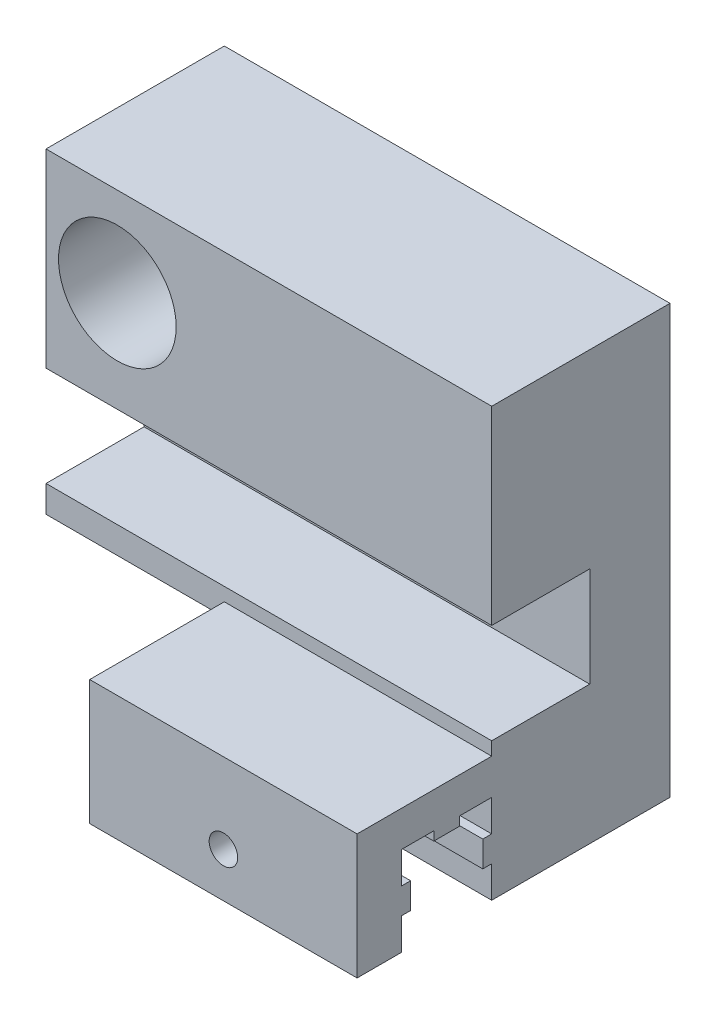
SolidWorks part; units mm, degrees
ref_plane "Front Plane" through (0, 0, 0) normal (0, 0, 1) x (1, 0, 0)
ref_plane "Top Plane" through (0, 0, 0) normal (0, 1, 0) x (1, 0, 0)
ref_plane "Right Plane" through (0, 0, 0) normal (1, 0, 0) x (0, 0, -1)
sketch "Esquisse1" plane through (0, 0, 0) normal (0, 0, 1) x (1, 0, 0)
  line L0 (25, 17.5) -> (25, -17.5)
  line L1 (-25, 17.5) -> (25, 17.5)
  line L2 (-25, 17.5) -> (-25, -17.5)
  line L3 (-25, -17.5) -> (25, -17.5)
  point P4 (-25, 0)
  point P6 (0, -17.5)
  point P7 (-9.098, 0)
  point P8 (13.0211, -17.5)
  point P9 (12.1692, -17.5)
  dimension "D3" = 35
  dimension "D4" = 50
extrude "Main Extrusion" add sketch "Esquisse1" along normal blind 20
sketch "Esquisse5" plane through (0, 0, 20) normal (0, 0, 1) x (1, 0, 0)
  line L1 (-25, -17.5) -> (25, -17.5) construction
  line L3 (-25, 17.5) -> (-25, -17.5) construction
  circle A0 centre (-17, 7.5) radius 1.6
  dimension "D1" = 3.2
  dimension "D2" = 25
  dimension "D3" = 8
extrude "Gear Linear Holes" cut sketch "Esquisse5" against normal through all
sketch "Esquisse8" plane through (0, 0, 0) normal (1, 0, 0) x (0, 0, -1)
  line L0 (-20, -20.5) -> (-20, -24.05)
  line L1 (-20, -20.5) -> (-23.6, -20.5)
  line L2 (-23.6, -20.5) -> (-23.6, -21.5)
  line L3 (-23.6, -21.5) -> (-26.5, -21.5)
  line L4 (-26.5, -21.5) -> (-26.5, -20.5)
  line L5 (-35.1, -16.5) -> (0, -16.5)
  line L6 (-20, -30.5) -> (0, -30.5)
  line L7 (0, -30.5) -> (0, -16.5)
  line L8 (0, -17.5) -> (0, 17.5) construction
  line L9 (-26.5, -20.5) -> (-30.1, -20.5)
  line L10 (-20, -17.5) -> (0, -17.5) construction
  line L12 (0, 17.5) -> (0, -17.5) construction
  line L13 (-30.1, -20.5) -> (-30.1, -24.05)
  line L14 (-30.1, -30.5) -> (-35.1, -30.5)
  line L15 (-35.1, -30.5) -> (-35.1, -16.5)
  line L16 (-20, -24.05) -> (-21, -24.05)
  line L17 (-21, -24.05) -> (-21, -26.95)
  line L18 (-21, -26.95) -> (-20, -26.95)
  line L19 (-20, -26.95) -> (-20, -30.5)
  line L21 (-30.1, -24.05) -> (-29.1, -24.05)
  line L22 (-29.1, -24.05) -> (-29.1, -26.95)
  line L23 (-29.1, -26.95) -> (-30.1, -26.95)
  line L24 (-30.1, -26.95) -> (-30.1, -30.5)
  line L25 (-20, 17.5) -> (-20, -17.5) construction
  point P12 (-17.324, -31.1687)
  point P18 (0, -17.5)
  point P19 (0, -15.4707)
  point P21 (0, 0)
  point P26 (-26.4545, -30.5)
  point P28 (-33.3936, -30.5)
  point P29 (0, 0)
  point P35 (0, -14.728)
  dimension "D1" = 2.9
  dimension "D2" = 10.1
  dimension "D3" = 1
  dimension "D4" = 3
  dimension "D5" = 10
  dimension "D6" = 5
  dimension "D7" = 4
extrude "Fixing Extrusion" add sketch "Esquisse8" along normal mid plane 50
sketch "Esquisse12" plane through (0, 0, 20) normal (0, 0, 1) x (1, 0, 0)
  circle A0 centre (-17, 7.5) radius 6.6
  dimension "D1" = 13.2
extrude "Enlèv. mat.-Extru.6" cut sketch "Esquisse12" against normal blind 10
sketch "Esquisse13" plane through (0, 0, 20) normal (0, 0, 1) x (1, 0, 0)
  line L0 (-25, 17.5) -> (-25, -16.5) construction
  line L1 (-25, -15) -> (25, -15)
  line L2 (-25, -15) -> (-25, -3.8)
  line L3 (-25, -3.8) -> (25, -3.8)
  line L4 (25, -15) -> (25, -3.8)
  line L5 (25, -16.5) -> (25, 17.5) construction
  line L7 (-25, -16.5) -> (25, -16.5) construction
  dimension "D1" = 1.5
  dimension "D2" = 11.2
extrude "Enlèv. mat.-Extru.7" cut sketch "Esquisse13" against normal blind 11
sketch "Esquisse14" plane through (-25, 0, 0) normal (-1, 0, 0) x (0, 0, 1)
  line L0 (0, -18) -> (20, -18)
  line L1 (0, -30.5) -> (35.1, -30.5)
  line L2 (0, -30.5) -> (0, -18)
  line L3 (20, -18) -> (20, -15)
  line L4 (35.1, -30.5) -> (35.1, -15)
  line L5 (20, -15) -> (35.1, -15)
  line L6 (20, -15) -> (20, -16.5) construction
  point P5 (35.1, -12.5069)
  point P8 (20, -15)
  dimension "D1" = 12.5
extrude "Enlèv. mat.-Extru.8" cut sketch "Esquisse14" against normal blind 20
sketch "Esquisse15" plane through (0, 0, 35.1) normal (0, 0, 1) x (1, 0, 0)
  line L1 (25, -16.5) -> (25, -30.5) construction
  line L4 (-5, -26.95) -> (-5, -24.05) construction
  circle A1 centre (10, -25.5) radius 1.6
  point P4 (0, 0)
  point P5 (-5, -25.5)
  dimension "D1" = 3.2
  dimension "D2" = 15
extrude "Enlèv. mat.-Extru.9" cut sketch "Esquisse15" against normal through all
